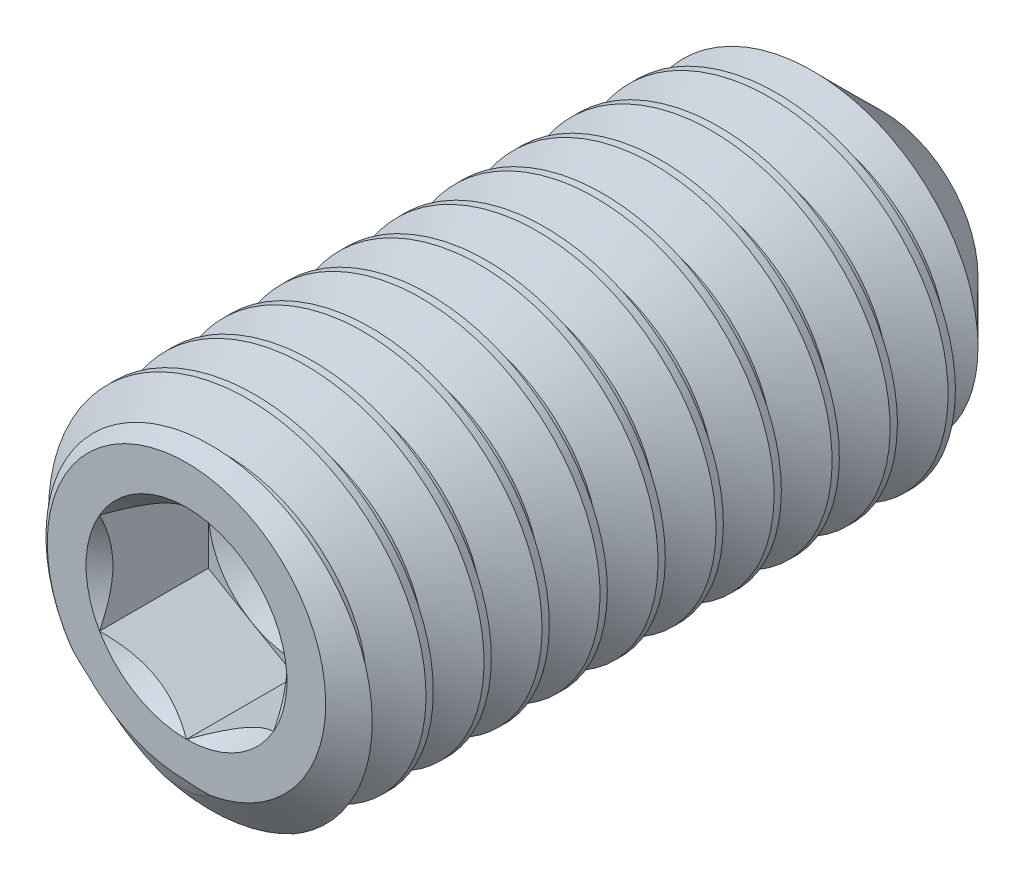
SolidWorks part; units mm, degrees
ref_plane "Front" through (0, 0, 0) normal (0, 0, 1) x (1, 0, 0)
ref_plane "Top" through (0, 0, 0) normal (0, 1, 0) x (1, 0, 0)
ref_plane "Right" through (0, 0, 0) normal (1, 0, 0) x (0, 0, -1)
sketch "Sketch22" plane through (0, 0, 0) normal (1, 0, 0) x (0, 0, -1)
  line L0 (-2.7531, 0) -> (-2.7531, 1.2)
  line L1 (-2.7531, 1.2) -> (-2.543, 1.5)
  line L2 (-2.543, 1.5) -> (2.5689, 1.5)
  line L3 (2.5689, 1.5) -> (3.2469, 0.8219)
  line L4 (3.2469, 0.8219) -> (2.7531, 0)
  line L5 (2.7531, 0) -> (-2.7531, 0)
  line L6 (2.7531, 0) -> (3.2469, 0) construction
  line L7 (3.2469, 0) -> (3.2469, 0.8219) construction
  line L8 (3.2469, -0.8219) -> (2.7531, 0) construction
  line L9 (-2.543, -1.5) -> (2.5689, -1.5) construction
  dimension "Dia" = 3
  dimension "Length" = 6
  dimension "D3" = 35
  dimension "D5" = 118
  dimension "D6" = 45
  dimension "D7" = 2.4
revolve "Revolve1" add sketch "Sketch22" angle 360 about L6
ref_plane "Plane1" through (0, 0, -3.2469) normal (0, 0, 1) x (1, 0, 0)
sketch "Sketch27" plane through (0, 0, -3.2469) normal (0, 0, 1) x (1, 0, 0)
  circle A0 centre (0, 0) radius 1.5 construction
  circle A1 centre (0, 0) radius 1.5
curve "Helix/Spiral1" pitch 0.5 height 6.5 turns 13
sketch "Sketch28" plane through (0, 0, 0) normal (1, 0, 0) x (0, 0, -1)
  line L0 (3.2469, 1.5) -> (3.6844, 1.5)
  line L1 (3.6844, 1.5) -> (3.4969, 1.1752)
  line L2 (3.4969, 1.1752) -> (3.4344, 1.1752)
  line L3 (3.4344, 1.1752) -> (3.2469, 1.5)
  line L4 (3.3407, 1.3376) -> (3.5907, 1.3376) construction
  line L6 (-2.543, 1.5) -> (2.5689, 1.5) construction
  dimension "D1" = 0.0625
  dimension "D2" = 0.25
  dimension "D3" = 60
sweep "Cut-Sweep2" cut profiles "Sketch28" path "Helix/Spiral1"
sketch "Sketch23" plane through (0, 0, 2.7531) normal (0, 0, 1) x (1, 0, 0)
  line L1 (0, 0.866) -> (-0.75, 0.433)
  line L2 (-0.75, 0.433) -> (-0.75, -0.433)
  line L3 (-0.75, -0.433) -> (0, -0.866)
  line L4 (0, -0.866) -> (0.75, -0.433)
  line L5 (0.75, -0.433) -> (0.75, 0.433)
  line L6 (0.75, 0.433) -> (0, 0.866)
  circle A0 centre (0, 0) radius 0.75 construction
  dimension "Hex" = 1.5
extrude "Cut-Extrude10" cut sketch "Sketch23" against normal blind 0.9375
sketch "Sketch24" plane through (0, 0, 2.7531) normal (0, 0, 1) x (1, 0, 0)
  circle A0 centre (0, 0) radius 0.866
extrude "Cut-Extrude11" cut sketch "Sketch24" against normal through all draft 45
sketch "Sketch26" plane through (0, 0, 1.8156) normal (0, 0, 1) x (1, 0, 0)
  circle A0 centre (0, 0) radius 0.75 construction
  circle A1 centre (0, 0) radius 0.75
extrude "Cut-Extrude12" cut sketch "Sketch26" against normal through all draft 60
sketch "Sketch30" plane through (0, 0, 0) normal (1, 0, 0) x (0, 0, -1)
  line L0 (-2.543, 1.5) -> (2.5689, 1.5) construction
  line L1 (-2.7531, 0) -> (-2.7531, 1.2) construction
  line L2 (3.2469, 0) -> (3.2469, 0.8219) construction
  line L3 (-2.543, -1.5) -> (2.5689, -1.5) construction
  point P0 (-2.7531, 1.5)
  point P1 (3.2469, 1.5)
  point P2 (3.2469, -1.5)
  point P11 (2.4969, -1.5)
  dimension "D1" = 0.75
sketch "Sketch31" plane through (0, 0, 0) normal (1, 0, 0) x (0, 0, -1)
  line L2 (2.7531, 0) -> (3.2469, -0.8219)
  line L3 (3.2469, 0.8219) -> (2.7531, 0)
equation "\"D7@Sketch22\"=\"Dia@Sketch22\"*.8"
equation "\"D1@Sketch28\" = \"D4@Helix/Spiral1\" * .125"
equation "\"D2@Sketch28\" = \"D4@Helix/Spiral1\" * .5"
equation "\"D3@Helix/Spiral1\" = \"Length@Sketch22\" + \"D4@Helix/Spiral1\""
equation "\"D1@Sketch30\" = \"D4@Helix/Spiral1\" * 1.5"
equation "\"hex Depth@Cut-Extrude10\" = \"Hex@Sketch23\" * .625"
